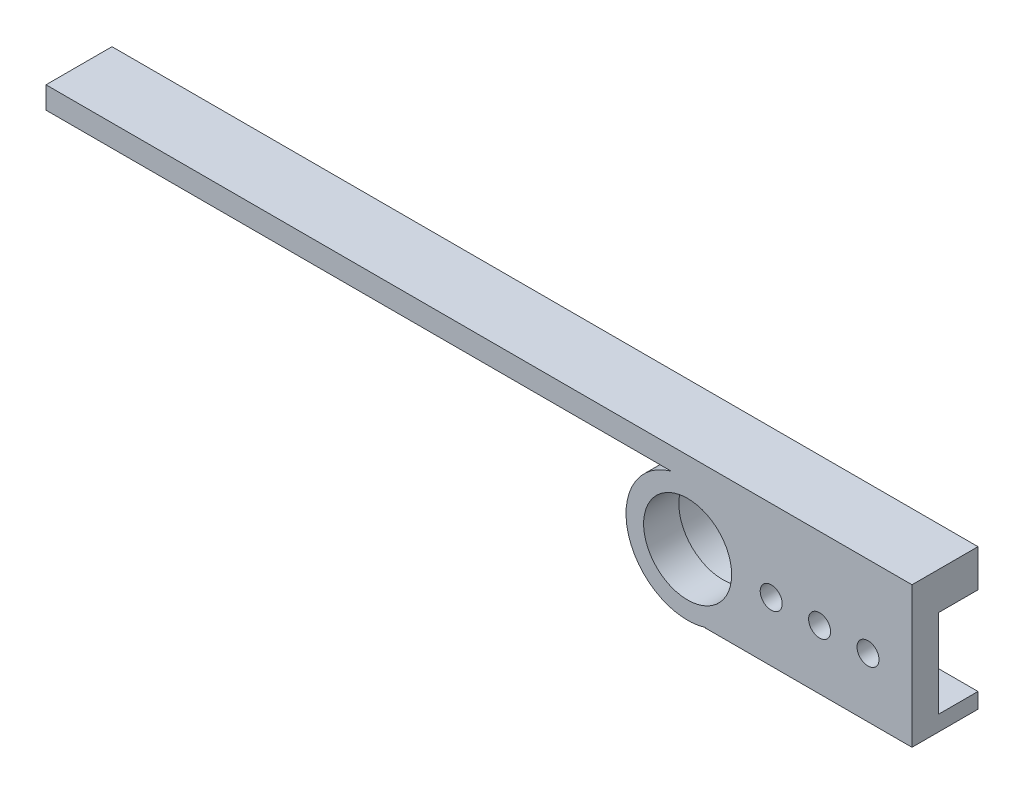
SolidWorks part; units mm, degrees
ref_plane "前视基准面" through (0, 0, 0) normal (0, 0, 1) x (1, 0, 0)
ref_plane "上视基准面" through (0, 0, 0) normal (0, 1, 0) x (1, 0, 0)
ref_plane "右视基准面" through (0, 0, 0) normal (1, 0, 0) x (0, 0, -1)
sketch "草图1" plane through (0, 0, 0) normal (0, 0, 1) x (1, 0, 0)
  line L1 (20, -10) -> (-20, -10)
  line L2 (20, -10) -> (20, 10)
  line L3 (20, 10) -> (-20, 10)
  line L4 (-20, -10) -> (-20, 10)
  line L5 (20, -10) -> (-20, 10) construction
  line L6 (20, 10) -> (-20, -10) construction
  point P0 (0, 0)
  dimension "D1" = 40
  dimension "D2" = 20
extrude "凸台-拉伸1" add sketch "草图1" along normal blind 6
sketch "草图2" plane through (0, 0, 6) normal (0, 0, 1) x (1, 0, 0)
  line L0 (20, -10) -> (20, 10) construction
  circle A0 centre (10, 0) radius 2.5
  circle A1 centre (-1, 0) radius 2.5
  circle A2 centre (-12, 0) radius 2.5
  dimension "D1" = 10
  dimension "D2" = 5
  dimension "D3" = 3
extrude "切除-拉伸1" cut sketch "草图2" against normal through all
sketch "草图3" plane through (0, 0, 6) normal (0, 0, 1) x (1, 0, 0)
  line L0 (20, 13.5) -> (20, 10)
  line L1 (20, -13.5) -> (-26.894, -13.5)
  line L3 (20, 13.5) -> (-26.894, 13.5)
  line L4 (-20, 10) -> (-20, -10)
  line L5 (-20, -10) -> (20, -10)
  line L6 (20, -10) -> (20, 10)
  line L7 (20, 10) -> (-20, 10)
  line L8 (-20, 10) -> (-20, -10)
  line L9 (-20, -10) -> (20, -10)
  line L10 (20, -10) -> (20, 10)
  line L11 (20, 10) -> (-20, 10)
  line L12 (-26.894, -13.5) -> (-26.894, 13.5)
  line L13 (20, -10.0394) -> (-26.894, 13.5) construction
  line L14 (20, 10.0394) -> (-26.894, -13.5) construction
  line L15 (20, -10) -> (20, -13.5)
  circle A0 centre (-31, 0) radius 11
  circle A1 centre (-31, 0) radius 14
  point P2 (0, 0)
  line M10 (-20, 10) -> (-20, -10)
  line M11 (-20, -10) -> (20, -10)
  line M13 (20, 10) -> (-20, 10)
  dimension "D3" = 22
  dimension "D4" = 28
  dimension "D2" = 3.5
  dimension "D1" = 0
extrude "凸台-拉伸2" add sketch "草图3" against normal blind 15 contours L3 A1 L1 L12 A0 | A1 L1 L15 M11 M10 | L1 A1 L8 A0 L12 | L8 A1 L3 L12 A0 | L8 A1 | A1 L0 L3 M10 M13 region at (-1.9449, 11.7771, 6) region at (-1.9449, -11.7771, 6) region at (-23.0173, 9.0328, 6) region at (-27.2274, 11.7946, 6) region at (-18.7882, 0, 6) region at (-23.0173, -9.0328, 6)
sketch "草图5" plane through (0, 0, 6) normal (0, 0, 1) x (1, 0, 0)
  circle A0 centre (-31, 0) radius 10
  circle A1 centre (-31, 0) radius 11 construction
  circle A2 centre (-31, 0) radius 11
  dimension "D1" = 20
extrude "凸台-拉伸3" add sketch "草图5" against normal blind 8
sketch "草图6" plane through (0, 0, 6) normal (0, 0, 1) x (1, 0, 0)
  circle A0 centre (-31, 0) radius 8.5
  circle A1 centre (-31, 0) radius 10 construction
  circle A2 centre (-31, 0) radius 10
  dimension "D1" = 17
sketch "草图7" plane through (0, 13.5, 0) normal (0, 1, 0) x (1, 0, 0)
  circle A0 centre (-16.8213, 3.0525) radius 3.3366
sketch "草图8" plane through (20, 0, 0) normal (1, 0, 0) x (0, 0, -1)
  line L1 (-6, 13.5) -> (9, 13.5)
  line L2 (-6, 13.5) -> (-6, 18.5)
  line L3 (-6, 18.5) -> (9, 18.5)
  line L4 (9, 13.5) -> (9, 18.5)
  dimension "D1" = 5
extrude "凸台-拉伸4" add sketch "草图8" against normal blind 200
sketch "草图9" plane through (0, 0, 6) normal (0, 0, 1) x (1, 0, 0)
  line L1 (-29.5663, 15.6648) -> (-25.1627, 15.6648)
  line L2 (-29.5663, 15.6648) -> (-29.5663, 11.9284)
  line L3 (-29.5663, 11.9284) -> (-25.1627, 11.9284)
  line L4 (-25.1627, 15.6648) -> (-25.1627, 11.9284)
extrude "凸台-拉伸5" add sketch "草图9" against normal through all
sketch "草图11" plane through (0, 18.5, 0) normal (0, 1, 0) x (1, 0, 0)
  line L0 (-118.4338, -6) -> (-118.4338, 9)
  line L1 (-180, -6) -> (20, -6) construction
  line L2 (-118.4338, 246.7017) -> (-118.4338, -123.2983) construction
  line L3 (-180, 9) -> (20, 9) construction
sketch "草图13" plane through (0, 18.5, 0) normal (0, 1, 0) x (1, 0, 0)
  line L1 (-118.4338, -6) -> (-183.1111, -6)
  line L2 (-118.4338, -6) -> (-118.4338, 12.5245)
  line L3 (-118.4338, 12.5245) -> (-183.1111, 12.5245)
  line L4 (-183.1111, -6) -> (-183.1111, 12.5245)
extrude "切除-拉伸2" cut sketch "草图13" against normal through all
sketch "草图14" plane through (0, 18.5, 0) normal (0, 1, 0) x (1, 0, 0)
  line L0 (-176.8267, 11.0465) -> (-176.8267, -39.4434)
  line L1 (-176.8267, 139.5002) -> (-176.8267, -230.4998) construction
sketch "草图15" plane through (0, 18.5, 0) normal (0, 1, 0) x (1, 0, 0)
  line L0 (-176.8267, 11.0465) -> (-176.8267, -39.4434) construction
  line L1 (-118.4338, -6) -> (-176.8267, -6)
  line L2 (-118.4338, -6) -> (-118.4338, 9)
  line L3 (-118.4338, 9) -> (-176.8267, 9)
  line L4 (-176.8267, -6) -> (-176.8267, 9)
extrude "凸台-拉伸6" add sketch "草图15" against normal blind 5
